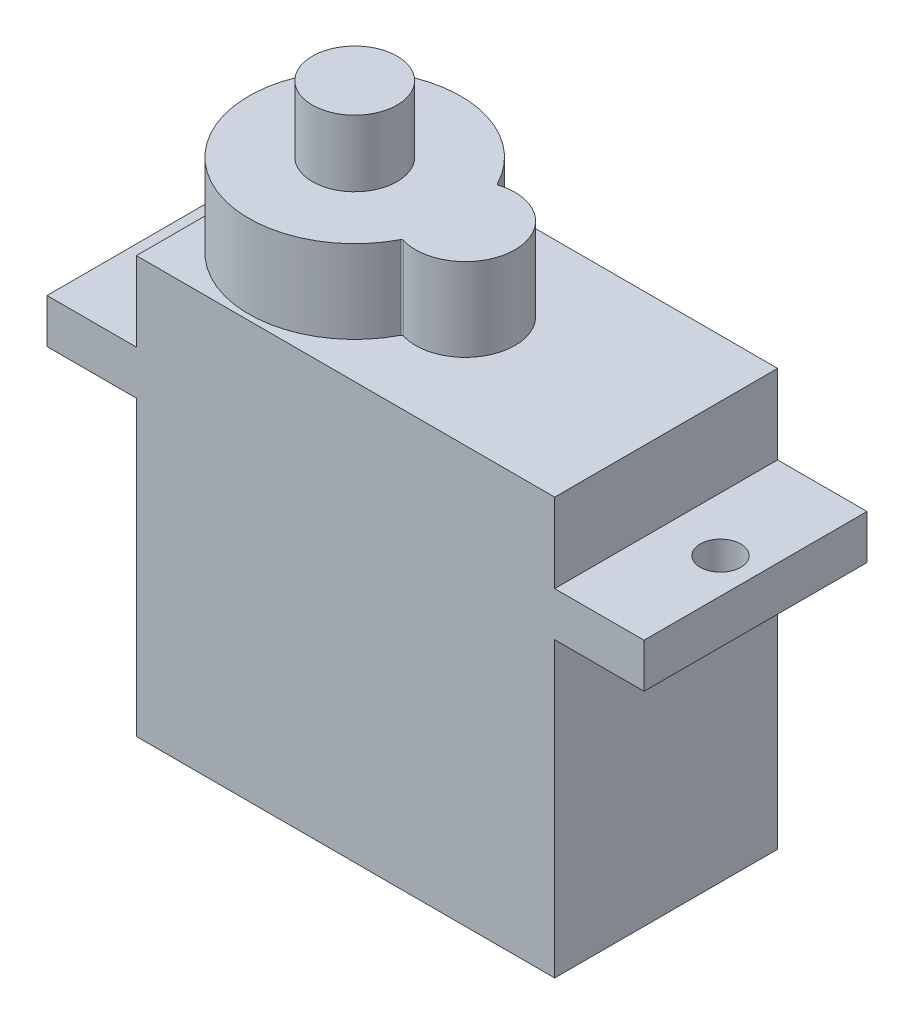
SolidWorks part; units mm, degrees
ref_plane "Front Plane" through (0, 0, 0) normal (0, 0, 1) x (1, 0, 0)
ref_plane "Top Plane" through (0, 0, 0) normal (0, 1, 0) x (1, 0, 0)
ref_plane "Right Plane" through (0, 0, 0) normal (1, 0, 0) x (0, 0, -1)
sketch "Sketch1" plane through (0, 0, 0) normal (0, 0, 1) x (1, 0, 0)
  line L0 (0, -4.3) -> (-4.85, -4.3)
  line L1 (0, 0) -> (22.7, 0)
  line L2 (0, 0) -> (0, -4.3)
  line L3 (0, -22.6) -> (22.7, -22.6)
  line L4 (22.7, 0) -> (22.7, -4.3)
  line L5 (-4.85, -4.3) -> (-4.85, -6.7)
  line L6 (-4.85, -6.7) -> (0, -6.7)
  line L7 (22.7, -6.7) -> (22.7, -22.6)
  line L8 (27.55, -6.7) -> (22.7, -6.7)
  line L9 (27.55, -4.3) -> (27.55, -6.7)
  line L10 (22.7, -4.3) -> (27.55, -4.3)
  line L11 (0, -6.7) -> (0, -22.6)
  dimension "D1" = 22.7
  dimension "D2" = 22.6
  dimension "D3" = 4.3
  dimension "D4" = 4.85
  dimension "D5" = 2.4
  dimension "D6" = 4.85
  dimension "D7" = 2.4
  dimension "D8" = 4.3
extrude "Boss-Extrude1" add sketch "Sketch1" along normal blind 12.1
sketch "Sketch3" plane through (0, -4.3, 0) normal (0, 1, 0) x (1, 0, 0)
  line L0 (0, -12.1) -> (-4.85, -12.1) construction
  line L1 (-4.85, -12.1) -> (-4.85, 0) construction
  line L2 (0, 0) -> (-4.85, 0) construction
  circle A0 centre (-2.95, -6.05) radius 1.1
  circle A1 centre (25.65, -6.05) radius 1.1
  dimension "D" = 2.2
  dimension "D1" = 6.05
  dimension "D2" = 1.9
  dimension "D3" = 6.05
  dimension "D5" = 30.5
extrude "Cut-Extrude1" cut sketch "Sketch3" against normal blind 12.1
sketch "Sketch4" plane through (0, 0, 0) normal (0, 1, 0) x (1, 0, 0)
  arc A0 (10.9477, -3.488) -> (10.9477, -8.612) centre (5.8, -6.05) ccw
  circle A1 centre (-2.95, -6.05) radius 1.1 construction
  arc A2 (10.9477, -8.612) -> (10.9477, -3.488) centre (11.8, -6.05) ccw
  dimension "D2" = 11.5
  dimension "D3" = 5.4
  dimension "D1" = 8.75
  dimension "D4" = 6
extrude "Boss-Extrude2" add sketch "Sketch4" along normal blind 4.5
fillet "Fillet1" radius 0.1 2 edges at (10.9477, 2.25, 3.488) (10.9477, 2.25, 8.612)
sketch "Sketch5" plane through (0, 4.5, 0) normal (0, 1, 0) x (1, 0, 0)
  circle A0 centre (5.8, -6.05) radius 2.3
  dimension "D1" = 4.6
extrude "Boss-Extrude3" add sketch "Sketch5" along normal blind 3.6
